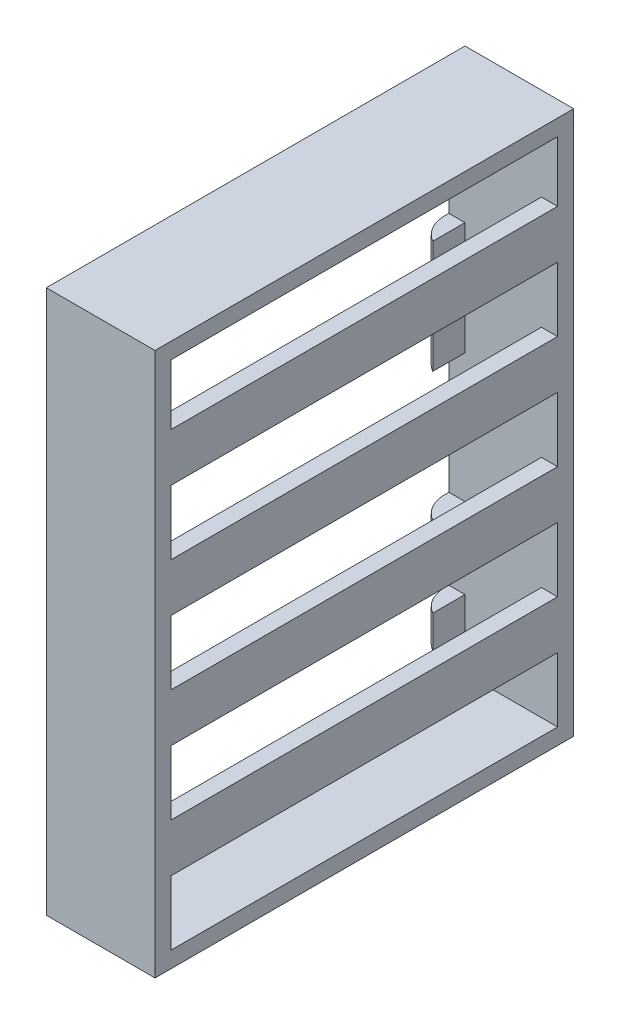
SolidWorks part; units mm, degrees
ref_plane "前视基准面" through (0, 0, 0) normal (0, 0, 1) x (1, 0, 0)
ref_plane "上视基准面" through (0, 0, 0) normal (0, 1, 0) x (1, 0, 0)
ref_plane "右视基准面" through (0, 0, 0) normal (1, 0, 0) x (0, 0, -1)
sketch "草图1" plane through (0, 0, 0) normal (0, 0, 1) x (1, 0, 0)
  line L1 (-2.7902, 8.4682) -> (10.7098, 8.4682)
  line L2 (-2.7902, 8.4682) -> (-2.7902, -59.0318)
  line L3 (-2.7902, -59.0318) -> (10.7098, -59.0318)
  line L4 (10.7098, 8.4682) -> (10.7098, -59.0318)
  dimension "D1" = 13.5
  dimension "D2" = 67.5
extrude "凸台-拉伸1" add sketch "草图1" along normal blind 52
sketch "草图2" plane through (10.7098, 0, 0) normal (1, 0, 0) x (0, 0, -1)
  line L0 (-52, 8.4682) -> (0, 8.4682) construction
  line L1 (-50, 6.4682) -> (-2, 6.4682)
  line L2 (-50, 6.4682) -> (-50, -57.0318)
  line L3 (-50, -57.0318) -> (-2, -57.0318)
  line L4 (-2, 6.4682) -> (-2, -57.0318)
  line L5 (0, -59.0318) -> (0, 8.4682) construction
  line L7 (-52, -59.0318) -> (-52, 8.4682) construction
  line L8 (-52, -59.0318) -> (0, -59.0318) construction
  dimension "D1" = 2
  dimension "D2" = 2
  dimension "D3" = 2
  dimension "D4" = 2
extrude "切除-拉伸1" cut sketch "草图2" against normal up to next
sketch "草图3" plane through (0, 0, 50) normal (0, 0, -1) x (-1, 0, 0)
  line L0 (2.7902, 6.4682) -> (-10.7098, 6.4682) construction
  line L1 (-10.7098, -1.0318) -> (-8.7098, -1.0318)
  line L2 (-10.7098, -1.0318) -> (-10.7098, -7.0318)
  line L3 (-10.7098, -7.0318) -> (-8.7098, -7.0318)
  line L4 (-8.7098, -1.0318) -> (-8.7098, -7.0318)
  line L5 (-10.7098, 6.4682) -> (-10.7098, -57.0318) construction
  line L22 (-10.7098, -15.0318) -> (-10.7098, -21.0318)
  line L23 (-10.7098, -15.0318) -> (-8.7098, -15.0318)
  line L24 (-8.7098, -15.0318) -> (-8.7098, -21.0318)
  line L25 (-10.7098, -21.0318) -> (-8.7098, -21.0318)
  line L26 (-10.7098, -29.0318) -> (-10.7098, -35.0318)
  line L27 (-10.7098, -29.0318) -> (-8.7098, -29.0318)
  line L28 (-8.7098, -29.0318) -> (-8.7098, -35.0318)
  line L29 (-10.7098, -35.0318) -> (-8.7098, -35.0318)
  line L30 (-10.7098, -43.0318) -> (-10.7098, -49.0318)
  line L31 (-10.7098, -43.0318) -> (-8.7098, -43.0318)
  line L32 (-8.7098, -43.0318) -> (-8.7098, -49.0318)
  line L33 (-10.7098, -49.0318) -> (-8.7098, -49.0318)
  point P8 (0.2902, -6.5318)
  point P12 (-9.7098, -36.5318)
  dimension "D1" = 2
  dimension "D2" = 6
  dimension "D3" = 7.5
  dimension "D4" = 4
extrude "凸台-拉伸2" add sketch "草图3" along normal up to next
sketch "草图9" plane through (0, 0, 50) normal (0, 0, -1) x (-1, 0, 0)
  line L0 (2.7902, -57.0318) -> (2.7902, 6.4682) construction
  line L1 (2.7902, 1.4682) -> (0.7902, 1.4682)
  line L2 (2.7902, 1.4682) -> (2.7902, -2.5318)
  line L3 (2.7902, -2.5318) -> (0.7902, -2.5318)
  line L4 (0.7902, 1.4682) -> (0.7902, -2.5318)
  line L5 (2.7902, 6.4682) -> (-10.7098, 6.4682) construction
  line L6 (2.7902, -8.5318) -> (2.7902, -12.5318)
  line L7 (2.7902, -8.5318) -> (0.7902, -8.5318)
  line L8 (0.7902, -8.5318) -> (0.7902, -12.5318)
  line L9 (2.7902, -12.5318) -> (0.7902, -12.5318)
  line L10 (2.7902, -18.5318) -> (2.7902, -22.5318)
  line L11 (2.7902, -18.5318) -> (0.7902, -18.5318)
  line L12 (0.7902, -18.5318) -> (0.7902, -22.5318)
  line L13 (2.7902, -22.5318) -> (0.7902, -22.5318)
  line L14 (2.7902, -28.5318) -> (2.7902, -32.5318)
  line L15 (2.7902, -28.5318) -> (0.7902, -28.5318)
  line L16 (0.7902, -28.5318) -> (0.7902, -32.5318)
  line L17 (2.7902, -32.5318) -> (0.7902, -32.5318)
  line L18 (2.7902, -38.5318) -> (2.7902, -42.5318)
  line L19 (2.7902, -38.5318) -> (0.7902, -38.5318)
  line L20 (0.7902, -38.5318) -> (0.7902, -42.5318)
  line L21 (2.7902, -42.5318) -> (0.7902, -42.5318)
  line L22 (2.7902, -48.5318) -> (2.7902, -52.5318)
  line L23 (2.7902, -48.5318) -> (0.7902, -48.5318)
  line L24 (0.7902, -48.5318) -> (0.7902, -52.5318)
  line L25 (2.7902, -52.5318) -> (0.7902, -52.5318)
  dimension "D1" = 2
  dimension "D2" = 4
  dimension "D3" = 5
  dimension "D4" = 6
extrude "凸台-拉伸3" add sketch "草图9" along normal blind 4
sketch "草图10" plane through (0, 6.4682, 0) normal (0, -1, 0) x (1, 0, 0)
  line L0 (-2.7902, 50) -> (-2.7902, 2) construction
  line L1 (-0.7902, 6) -> (-2.7902, 6)
  line L2 (-0.7902, 6) -> (-0.7902, 10)
  line L3 (-0.7902, 10) -> (-2.7902, 10)
  line L4 (-2.7902, 6) -> (-2.7902, 10)
  line L5 (-2.7902, 2) -> (10.7098, 2) construction
  line L6 (-0.7902, 15) -> (-0.7902, 19)
  line L7 (-0.7902, 15) -> (-2.7902, 15)
  line L8 (-2.7902, 15) -> (-2.7902, 19)
  line L9 (-0.7902, 19) -> (-2.7902, 19)
  line L10 (-0.7902, 24) -> (-0.7902, 28)
  line L11 (-0.7902, 24) -> (-2.7902, 24)
  line L12 (-2.7902, 24) -> (-2.7902, 28)
  line L13 (-0.7902, 28) -> (-2.7902, 28)
  line L14 (-0.7902, 33) -> (-0.7902, 37)
  line L15 (-0.7902, 33) -> (-2.7902, 33)
  line L16 (-2.7902, 33) -> (-2.7902, 37)
  line L17 (-0.7902, 37) -> (-2.7902, 37)
  line L18 (-0.7902, 42) -> (-0.7902, 46)
  line L19 (-0.7902, 42) -> (-2.7902, 42)
  line L20 (-2.7902, 42) -> (-2.7902, 46)
  line L21 (-0.7902, 46) -> (-2.7902, 46)
  point P8 (-1.7902, 46)
  dimension "D1" = 2
  dimension "D2" = 4
  dimension "D3" = 4
  dimension "D4" = 5
extrude "凸台-拉伸4" add sketch "草图10" along normal blind 4
sketch "草图11" plane through (0, -57.0318, 0) normal (0, 1, 0) x (1, 0, 0)
  line L0 (-2.7902, -2) -> (-2.7902, -50) construction
  line L1 (-2.7902, -42) -> (-0.7902, -42)
  line L2 (-2.7902, -42) -> (-2.7902, -46)
  line L3 (-2.7902, -46) -> (-0.7902, -46)
  line L4 (-0.7902, -42) -> (-0.7902, -46)
  line L5 (-2.7902, -50) -> (10.7098, -50) construction
  line L6 (-2.7902, -33) -> (-2.7902, -37)
  line L7 (-2.7902, -33) -> (-0.7902, -33)
  line L8 (-0.7902, -33) -> (-0.7902, -37)
  line L9 (-2.7902, -37) -> (-0.7902, -37)
  line L10 (-2.7902, -24) -> (-2.7902, -28)
  line L11 (-2.7902, -24) -> (-0.7902, -24)
  line L12 (-0.7902, -24) -> (-0.7902, -28)
  line L13 (-2.7902, -28) -> (-0.7902, -28)
  line L14 (-2.7902, -15) -> (-2.7902, -19)
  line L15 (-2.7902, -15) -> (-0.7902, -15)
  line L16 (-0.7902, -15) -> (-0.7902, -19)
  line L17 (-2.7902, -19) -> (-0.7902, -19)
  line L18 (-2.7902, -6) -> (-2.7902, -10)
  line L19 (-2.7902, -6) -> (-0.7902, -6)
  line L20 (-0.7902, -6) -> (-0.7902, -10)
  line L21 (-2.7902, -10) -> (-0.7902, -10)
  point P8 (-1.7902, -46)
  dimension "D1" = 2
  dimension "D2" = 4
  dimension "D3" = 4
  dimension "D4" = 5
extrude "凸台-拉伸5" add sketch "草图11" along normal blind 4
sketch "草图12" plane through (0, 0, 2) normal (0, 0, 1) x (1, 0, 0)
  line L0 (-2.7902, 6.4682) -> (-2.7902, -57.0318) construction
  line L1 (-0.7902, -2.5318) -> (-2.7902, -2.5318)
  line L2 (-0.7902, -2.5318) -> (-0.7902, 1.4682)
  line L3 (-0.7902, 1.4682) -> (-2.7902, 1.4682)
  line L4 (-2.7902, -2.5318) -> (-2.7902, 1.4682)
  line L5 (-2.7902, 6.4682) -> (10.7098, 6.4682) construction
  line L6 (-0.7902, -12.5318) -> (-0.7902, -8.5318)
  line L7 (-0.7902, -12.5318) -> (-2.7902, -12.5318)
  line L8 (-2.7902, -12.5318) -> (-2.7902, -8.5318)
  line L9 (-0.7902, -8.5318) -> (-2.7902, -8.5318)
  line L10 (-0.7902, -22.5318) -> (-0.7902, -18.5318)
  line L11 (-0.7902, -22.5318) -> (-2.7902, -22.5318)
  line L12 (-2.7902, -22.5318) -> (-2.7902, -18.5318)
  line L13 (-0.7902, -18.5318) -> (-2.7902, -18.5318)
  line L14 (-0.7902, -32.5318) -> (-0.7902, -28.5318)
  line L15 (-0.7902, -32.5318) -> (-2.7902, -32.5318)
  line L16 (-2.7902, -32.5318) -> (-2.7902, -28.5318)
  line L17 (-0.7902, -28.5318) -> (-2.7902, -28.5318)
  line L18 (-0.7902, -42.5318) -> (-0.7902, -38.5318)
  line L19 (-0.7902, -42.5318) -> (-2.7902, -42.5318)
  line L20 (-2.7902, -42.5318) -> (-2.7902, -38.5318)
  line L21 (-0.7902, -38.5318) -> (-2.7902, -38.5318)
  line L22 (-0.7902, -52.5318) -> (-0.7902, -48.5318)
  line L23 (-0.7902, -52.5318) -> (-2.7902, -52.5318)
  line L24 (-2.7902, -52.5318) -> (-2.7902, -48.5318)
  line L25 (-0.7902, -48.5318) -> (-2.7902, -48.5318)
  dimension "D1" = 4
  dimension "D2" = 2
  dimension "D3" = 5
  dimension "D4" = 6
extrude "凸台-拉伸6" add sketch "草图12" along normal blind 4
fillet "圆角1" radius 4 22 edges at (-2.7902, -50.5318, 46) (-2.7902, -53.0318, 44) (-2.7902, -40.5318, 46) (-2.7902, -30.5318, 46) (-2.7902, -53.0318, 35) (-2.7902, -53.0318, 26) (-2.7902, -53.0318, 17) (-2.7902, -50.5318, 6) (-2.7902, -53.0318, 8) (-2.7902, -40.5318, 6) (-2.7902, -20.5318, 6) (-2.7902, -30.5318, 6) (-2.7902, -10.5318, 6) (-2.7902, -0.5318, 6) (-2.7902, 2.4682, 8) (-2.7902, 2.4682, 17) (-2.7902, 2.4682, 26) (-2.7902, 2.4682, 35) (-2.7902, 2.4682, 44) (-2.7902, -0.5318, 46) (-2.7902, -10.5318, 46) (-2.7902, -20.5318, 46)
